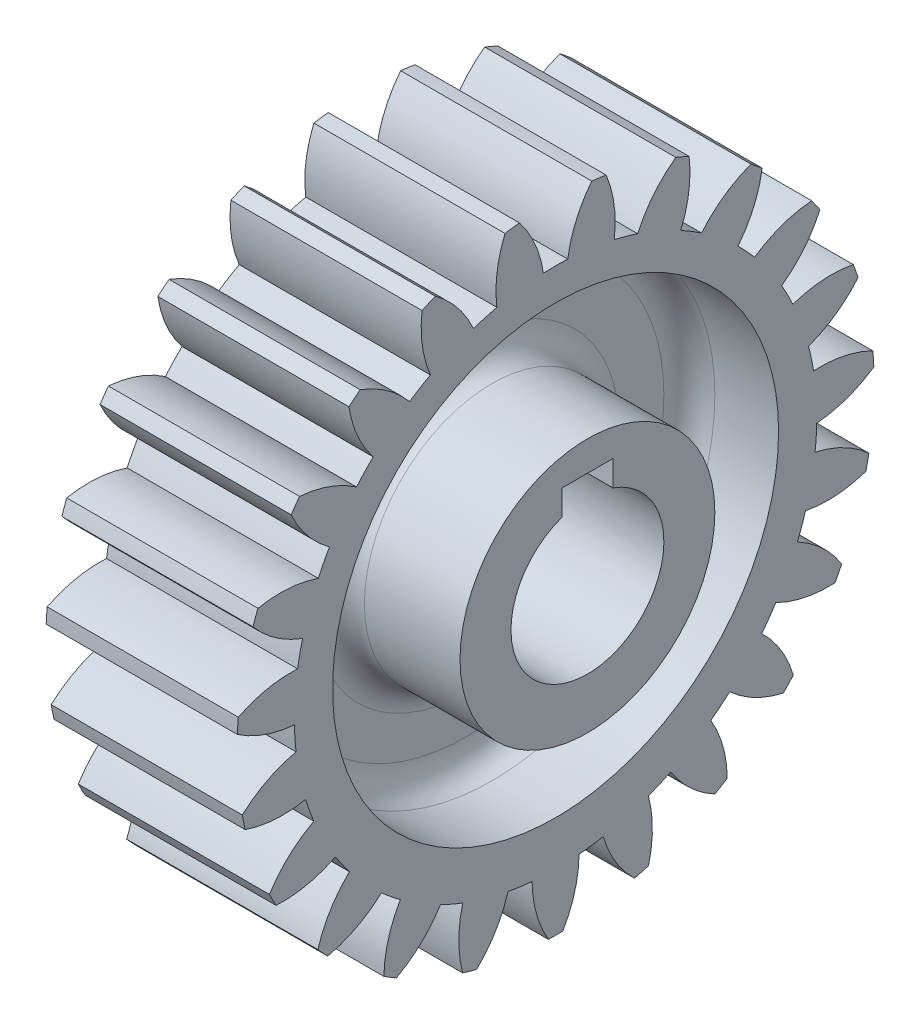
SolidWorks part; units mm, degrees
ref_plane "Plane1" through (0, 0, 0) normal (0, 0, 1) x (1, 0, 0)
ref_plane "Plane2" through (0, 0, 0) normal (0, 1, 0) x (1, 0, 0)
ref_plane "Plane3" through (0, 0, 0) normal (1, 0, 0) x (0, 0, -1)
other "Configuration Table"
sketch "HoldingSke" plane through (0, 0, 0) normal (0, 1, 0) x (1, 0, 0)
  line L0 (0, 0) -> (0.2301, -0.0977)
  line L1 (-15, 0) -> (100, 0) construction
  line L2 (0, 0) -> (-2.1039, 2.3779)
  line L3 (0, 0) -> (-11.863, 4.5341)
  line L4 (0, 0) -> (7.9495, 3.3744)
  line L5 (0, 0) -> (-37.4781, -13.9782)
  line L6 (0, 0) -> (-24.8689, -16.7791)
  line L7 (-2.1039, 2.3779) -> (6.5061, 41.4403)
  line L8 (-76.2, 54.61) -> (-72.9, 54.61)
  line L9 (-71.009, 38.7566) -> (-53.1078, 45.2721)
  line L10 (-76.2, 71.12) -> (104.1128, 71.12)
  line L11 (0, 0) -> (-30, 0)
  line L12 (-76.2, 101.6) -> (-76.073, 101.6)
  line L13 (24.9733, 27.94) -> (52.9518, 28.4284)
  line L14 (24.9733, 27.94) -> (24.9743, 27.94)
  line L15 (24.9733, 27.94) -> (100.4006, 29.5858)
  line L16 (-63.627, -4) -> (-12.827, -4)
  circle A0 centre (0, 0) radius 12
  circle A1 centre (0, 0) radius 20
  circle A2 centre (0, 0) radius 20
  circle A3 centre (0, 0) radius 12
  dimension "Num_teeth" = 23
  dimension "Pitch_radius" = 180.3128
  dimension "Width" = 30
  dimension "Thickness" = 30
sketch "BasProSke" plane through (0, 0, 0) normal (0, 1, 0) x (1, 0, 0)
  line L0 (-10, 0) -> (60, 0) construction
  line L1 (0, 0) -> (0, 50)
  line L2 (0, 0) -> (30, 0)
  line L3 (30, 0) -> (30, 50)
  line L4 (30, 50) -> (0, 50)
  dimension "Thickness" = 30
  dimension "Diameter" = 100
revolve "Base-Revolve" add sketch "BasProSke" angle 360 about L0
sketch "TooCutSke" plane through (0, 0, 0) normal (1, 0, 0) x (0, 0, -1)
  line L1 (0, 0) -> (0, 107) construction
  line L2 (0, 0) -> (-3.3613, 45.877) construction
  line L3 (0, 0) -> (-12.5021, 90.9597) construction
  line L4 (-3.3613, 45.877) -> (-6.2511, 45.4798) construction
  arc A0 (1.9097, 40.9545) -> (-1.9097, 40.9545) centre (0, 0) ccw
  arc A1 (5.6984, 49.6998) -> (-5.6984, 49.6998) centre (0, 0) ccw
  circle A2 centre (0, 0) radius 46 construction
  circle A3 centre (0, 0) radius 43.2259 construction
  arc A4 (-1.9097, 40.9545) -> (-5.6984, 49.6998) centre (-20.1117, 38.2622) ccw
  arc A5 (5.6984, 49.6998) -> (1.9097, 40.9545) centre (20.1117, 38.2622) ccw
extrude "ToothCut" cut sketch "TooCutSke" along normal through all
fillet "Breaks" [suppressed] radius 0.08 tangent propagation no
fillet "RootFillets" [suppressed] radius 1.001
pattern_circular "TeethCuts" count 23 every 15.652 about axis through (-10, 0, 0) along (1, 0, 0) of "ToothCut", "RootFillets", "Breaks"
sketch "HubNeaOneSke" plane through (0, 0, 0) normal (-1, 0, 0) x (0, 0, 1)
  circle A0 centre (0, 0) radius 20
  dimension "Diameter" = 40
extrude "HubNearOne" [suppressed] add sketch "HubNeaOneSke" along normal blind 10.0001
sketch "HubNeaBotSke" plane through (0, 0, 0) normal (-1, 0, 0) x (0, 0, 1)
  circle A0 centre (0, 0) radius 20
  dimension "Diameter" = 40
extrude "HubNearBoth" add sketch "HubNeaBotSke" along normal blind 5
ref_plane "FarPln" through (30, 0, 0) normal (1, 0, 0) x (0, 0, -1)
sketch "HubFarSke" plane through (30, 0, 0) normal (1, 0, 0) x (0, 0, -1)
  circle A0 centre (0, 0) radius 20
  dimension "Diameter" = 40
extrude "HubFar" add sketch "HubFarSke" along normal blind 5
sketch "BorSke" plane through (0, 0, 0) normal (1, 0, 0) x (0, 0, -1)
  circle A0 centre (0, 0) radius 12
  dimension "Diameter" = 24
extrude "Bore" cut sketch "BorSke" along normal mid plane 80.0001
sketch "KeySke" plane through (0, 0, 0) normal (1, 0, 0) x (0, 0, -1)
  line L0 (-4, 0) -> (-4, 15.3)
  line L1 (-4, 15.3) -> (4, 15.3)
  line L2 (4, 15.3) -> (4, 0)
  line L3 (0, 0) -> (0, 34) construction
  line L4 (-4, 0) -> (4, 0)
  dimension "Width" = 8
extrude "Keyway" cut sketch "KeySke" along normal mid plane 80.0001
pattern_circular "Keyway2" [suppressed] count 2 every 90 about axis through (-10, 0, 0) along (1, 0, 0) reverse direction yes
sketch "Sketch1" plane through (30, 0, 0) normal (1, 0, 0) x (0, 0, -1)
  circle A0 centre (0, 0) radius 20
  circle A1 centre (0, 0.9809) radius 35
extrude "Cut-Extrude1" cut sketch "Sketch1" against normal blind 14
fillet "Fillet1" radius 4 2 edges at (16, 0, -20) (16, 0.9809, -35)
sketch "Sketch2" plane through (0, 0, 0) normal (-1, 0, 0) x (0, 0, 1)
  circle A0 centre (0, 0) radius 20
  circle A1 centre (0, 0) radius 35
extrude "Cut-Extrude2" cut sketch "Sketch2" against normal blind 14
fillet "Fillet2" radius 4 2 edges at (14, 0, 20) (14, 0, 35)
equation "' \"Module@HoldingSke\" = 6.35"
equation "' \"Num_teeth@HoldingSke\" = 12"
equation "' \"Ap@HoldingSke\" =  20"
equation "' \"Ap@HoldingSke\" = 20"
equation "' \"Width@HoldingSke\" = 0.5 * 25.4"
equation "' \"Hub_dia@HoldingSke\"= 1 * 25.4"
equation "' \"Hub_dia@HoldingSke\" = 1 * 25.4"
equation "' \"Overall_len@HoldingSke\" = 1.0 * 25.4"
equation "' \"Bore@HoldingSke\" = 0.75 * 25.4"
equation "' \"T_dim@HoldingSke\" = 0.1 * 25.4"
equation "' \"Width@KeySke\" = 0.25 * 25.4"
equation "' \"Show_teeth@HoldingSke\" = 13"
equation "' \"Backlash@HoldingSke\" = 0.009 * 25.4"
equation "' \"Addendum_fac@HoldingSke\" = 1.0"
equation "' \"Dedendum_fac@HoldingSke\" = 1.25"
equation "' \"Dedendum_add@HoldingSke\" = 0.00005 * 25.4"
equation "' \"Clearance_fac@HoldingSke\" = 0.25"
equation "\"Pitch@HoldingSke\" = 1 / \"Module@HoldingSke\""
equation "\"Overcut_dia@TooCutSke\" = (\"Num_teeth@HoldingSke\" + 2 * \"Addendum_fac@HoldingSke\") / \"Pitch@HoldingSke\" + 0.002 * 25.4"
equation "\"Pitch_dia@TooCutSke\" = \"Num_teeth@HoldingSke\" / \"Pitch@HoldingSke\""
equation "\"Base_dia@TooCutSke\" = \"Num_teeth@HoldingSke\" / \"Pitch@HoldingSke\" * cos((\"Ap@HoldingSke\"  * 3.14159265 / 180))"
equation "\"Root_dia@TooCutSke\" = (\"Num_teeth@HoldingSke\" + 2) / \"Pitch@HoldingSke\" - 2 * (\"Addendum_fac@HoldingSke\" + \"Dedendum_fac@HoldingSke\") / \"Pitch@HoldingSke\" - \"Dedendum_add@HoldingSke\" * 2"
equation "\"Half_ang@TooCutSke\" = 180 / \"Num_teeth@HoldingSke\""
equation "\"Half_CT@TooCutSke\" = \"Num_teeth@HoldingSke\" / \"Pitch@HoldingSke\" * sin((3.14159265 / 2 / \"Num_teeth@HoldingSke\")) / 2 - 7 * \"Backlash@HoldingSke\" / 4"
equation "\"Flank_rad@TooCutSke\" = \"Num_teeth@HoldingSke\" / \"Pitch@HoldingSke\" / 5"
equation "\"Radius@RootFillets\" = \"Clearance_fac@HoldingSke\" / \"Pitch@HoldingSke\" + \"Dedendum_add@HoldingSke\""
equation "\"Break_rad@Breaks\" = 0.02 / \"Pitch@HoldingSke\""
equation "\"Thickness@HoldingSke\" = \"Width@HoldingSke\""
equation "\"OAL@HoldingSke\" = \"Thickness@HoldingSke\""
equation "\"MHD@HoldingSke\" = (\"Num_teeth@HoldingSke\" + 2) / \"Pitch@HoldingSke\" - 2 * (\"Addendum_fac@HoldingSke\" + \"Dedendum_fac@HoldingSke\")  / \"Pitch@HoldingSke\" - \"Dedendum_add@HoldingSke\" * 2"
equation "\"MBD@HoldingSke\" = (\"Num_teeth@HoldingSke\" + 2) / \"Pitch@HoldingSke\" - 2 * (\"Addendum_fac@HoldingSke\" + \"Dedendum_fac@HoldingSke\")  / \"Pitch@HoldingSke\" - \"Dedendum_add@HoldingSke\" * 2 - 0.002 * 25.4"
equation "\"MHD@HoldingSke\" = ((sgn( \"MHD@HoldingSke\" - \"Hub_dia@HoldingSke\" )-1)*( \"MHD@HoldingSke\" - \"Hub_dia@HoldingSke\" ))/-2+ \"Hub_dia@HoldingSke\""
equation "\"MBD@HoldingSke\" = ((sgn( \"MBD@HoldingSke\" - \"Bore@HoldingSke\" )-1)*( \"MBD@HoldingSke\" - \"Bore@HoldingSke\" ))/-2+ \"Bore@HoldingSke\""
equation "\"OAL@HoldingSke\" = ((sgn( \"OAL@HoldingSke\" - \"Overall_len@HoldingSke\" )+1)*( \"OAL@HoldingSke\" - \"Overall_len@HoldingSke\" ))/2 + \"Overall_len@HoldingSke\" + 0.000002 * 25.4"
equation "\"Num_teeth@TeethCuts\" = int( \"Show_teeth@HoldingSke\" ) + 1"
equation "\"Num_teeth@TeethCuts\" = ((sgn( \"Num_teeth@TeethCuts\" - \"Num_teeth@HoldingSke\" )-1)*( \"Num_teeth@TeethCuts\" - \"Num_teeth@HoldingSke\" ))/-2+ \"Num_teeth@HoldingSke\""
equation "\"Num_teeth@TeethCuts\" = ((sgn( \"Num_teeth@TeethCuts\" - 2.0)+1)*( \"Num_teeth@TeethCuts\" - 2.0))/2 +2.0"
equation "\"Angle@TeethCuts\" = 360.0 / \"Num_teeth@HoldingSke\""
equation "\"Diameter@BasProSke\" = (\"Num_teeth@HoldingSke\" + 2 * \"Addendum_fac@HoldingSke\") / \"Pitch@HoldingSke\""
equation "\"Thickness@BasProSke\"  = \"Thickness@HoldingSke\""
equation "' \"Fillet_rad@BasProSke\" =  \"Thickness@HoldingSke\" * 0.05"
equation "' \"Fillet_rad@BasProSke\" = \"Thickness@HoldingSke\" * 0.05"
equation "\"MHD@HoldingSke\" = ((sgn( \"MHD@HoldingSke\" - \"Root_dia@TooCutSke\" )-1)*( \"MHD@HoldingSke\" - \"Root_dia@TooCutSke\" ))/-2+ \"Root_dia@TooCutSke\""
equation "\"Diameter@HubNeaOneSke\" = \"MHD@HoldingSke\""
equation "\"Length@HubNearOne\" = \"OAL@HoldingSke\" - \"Thickness@BasProSke\""
equation "\"Diameter@HubNeaBotSke\" = \"MHD@HoldingSke\""
equation "\"Length@HubNearBoth\" = ( \"OAL@HoldingSke\" - \"Thickness@BasProSke\" ) / 2.0"
equation "\"Thickness@FarPln\" = \"Thickness@BasProSke\""
equation "\"Diameter@HubFarSke\" = \"MHD@HoldingSke\""
equation "\"Length@HubFar\" = ( \"OAL@HoldingSke\" - \"Thickness@BasProSke\" ) / 2.0"
equation "\"Diameter@BorSke\" = \"MBD@HoldingSke\""
equation "\"D1@Bore\" = \"OAL@HoldingSke\" * 2.0"
equation "\"D1@Keyway\" = \"OAL@HoldingSke\" * 2.0"
equation "\"Offset@KeySke\" = \"T_dim@HoldingSke\" + \"MBD@HoldingSke\" / 2.0"
